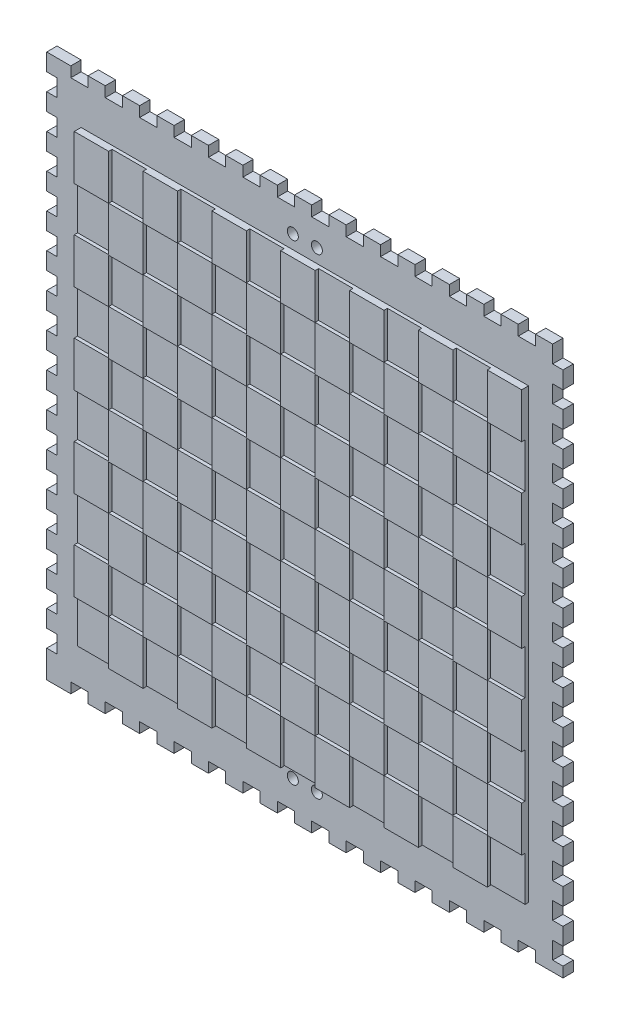
SolidWorks part; units mm, degrees
ref_plane "Front Plane" through (0, 0, 0) normal (0, 0, 1) x (1, 0, 0)
ref_plane "Top Plane" through (0, 0, 0) normal (0, 1, 0) x (1, 0, 0)
ref_plane "Right Plane" through (0, 0, 0) normal (1, 0, 0) x (0, 0, -1)
sketch "Sketch1" plane through (0, 0, 0) normal (0, 0, 1) x (1, 0, 0)
  line L5 (-75, 79) -> (75, 79)
  line L6 (-75, 79) -> (-75, -79)
  line L7 (-75, -79) -> (75, -79)
  line L8 (75, 79) -> (75, -79)
  line L9 (-75, 79) -> (75, -79) construction
  line L10 (-75, -79) -> (75, 79) construction
  point P0 (0, 0)
  dimension "D1" = 158
  dimension "D2" = 150
extrude "Boss-Extrude1" add sketch "Sketch1" along normal blind 5
sketch "Sketch2" plane through (0, 0, 5) normal (0, 0, 1) x (1, 0, 0)
  line L1 (-65, 65) -> (65, 65)
  line L2 (-65, 65) -> (-65, -65)
  line L3 (-65, -65) -> (65, -65)
  line L4 (65, 65) -> (65, -65)
  line L5 (-65, 65) -> (65, -65) construction
  line L6 (-65, -65) -> (65, 65) construction
  point P0 (0, 0)
  dimension "D1" = 130
  dimension "D2" = 130
extrude "Cut-Extrude1" cut sketch "Sketch2" against normal blind 1
sketch "Sketch3" plane through (0, 0, 4) normal (0, 0, 1) x (1, 0, 0)
  line L1 (-65, 65) -> (-55, 65)
  line L2 (-65, 65) -> (-65, 51.9)
  line L3 (-65, 51.9) -> (-55, 51.9)
  line L4 (-55, 65) -> (-55, 51.9)
  dimension "D1" = 13.1
  dimension "D2" = 10
extrude "Boss-Extrude2" add sketch "Sketch3" along normal blind 1
sketch "Sketch5" plane through (0, 0, 5) normal (0, 0, 1) x (1, 0, 0)
  line L1 (65, -65) -> (-65, -65)
  line L2 (65, -65) -> (65, 65)
  line L3 (65, 65) -> (-65, 65)
  line L4 (-65, -65) -> (-65, 65)
  line L9 (-75, -79) -> (75, -79)
  line L10 (-75, -79) -> (-75, 79)
  line L11 (-75, 79) -> (75, 79)
  line L12 (75, -79) -> (75, 79)
  dimension "D1" = 130
  dimension "D2" = 130
extrude "Cut-Extrude6" cut sketch "Sketch5" against normal blind 2
pattern_linear "LPattern3" count 7 spacing 20 along (1, 0, 0) count 5 spacing 26 along (0, -1, 0) of "Boss-Extrude2"
sketch "Sketch11" plane through (0, 0, 4) normal (0, 0, 1) x (1, 0, 0)
  line L0 (65, 65) -> (-65, 65) construction
  line L1 (-55, 51.95) -> (-45, 51.95)
  line L2 (-55, 51.95) -> (-55, 38.85)
  line L3 (-55, 38.85) -> (-45, 38.85)
  line L4 (-45, 51.95) -> (-45, 38.85)
  line L5 (-65, 65) -> (-65, -65) construction
  dimension "D1" = 13.1
  dimension "D2" = 10
  dimension "D3" = 13.05
  dimension "D4" = 10
extrude "Boss-Extrude4" add sketch "Sketch11" along normal blind 1
pattern_linear "LPattern4" count 6 spacing 20 along (1, 0, 0) count 5 spacing 26 along (0, -1, 0) of "Boss-Extrude4"
sketch "Sketch12" plane through (0, 0, 3) normal (0, 0, 1) x (1, 0, 0)
  line L1 (75, 79) -> (72, 79)
  line L2 (75, 79) -> (75, 74)
  line L3 (75, 74) -> (72, 74)
  line L4 (72, 79) -> (72, 74)
  dimension "D1" = 3
  dimension "D2" = 5
extrude "Cut-Extrude10" cut sketch "Sketch12" against normal through all
pattern_linear "LPattern5" count 16 spacing 10 along (0, -1, 0) of "Cut-Extrude10"
sketch "Sketch13" plane through (0, 0, 3) normal (0, 0, 1) x (1, 0, 0)
  line L0 (72, 79) -> (-75, 79) construction
  line L1 (67, 79) -> (62, 79)
  line L2 (67, 79) -> (67, 76)
  line L3 (67, 76) -> (62, 76)
  line L4 (62, 79) -> (62, 76)
  line L5 (72, 79) -> (72, 74) construction
  dimension "D1" = 5
  dimension "D2" = 3
  dimension "D3" = 5
extrude "Cut-Extrude11" cut sketch "Sketch13" against normal blind 3
pattern_linear "LPattern6" count 14 spacing 10 along (-1, 0, 0) of "Cut-Extrude11"
sketch "Sketch14" plane through (0, 0, 3) normal (0, 0, 1) x (1, 0, 0)
  line L0 (-75, -79) -> (75, -79) construction
  line L1 (67, -79) -> (62, -79)
  line L2 (67, -79) -> (67, -76)
  line L3 (67, -76) -> (62, -76)
  line L4 (62, -79) -> (62, -76)
  dimension "D1" = 5
  dimension "D2" = 3
  dimension "D3" = 5
extrude "Cut-Extrude12" cut sketch "Sketch14" against normal blind 3
pattern_linear "LPattern7" count 14 spacing 10 along (-1, 0, 0) of "Cut-Extrude12"
sketch "Sketch15" plane through (0, 0, 3) normal (0, 0, 1) x (1, 0, 0)
  line L0 (-75, 79) -> (-75, -79) construction
  line L1 (-75, 74) -> (-72, 74)
  line L2 (-75, 74) -> (-75, 69)
  line L3 (-75, 69) -> (-72, 69)
  line L4 (-72, 74) -> (-72, 69)
  line L5 (-68, 79) -> (-75, 79) construction
  dimension "D1" = 5
  dimension "D2" = 5
  dimension "D3" = 3
extrude "Cut-Extrude13" cut sketch "Sketch15" against normal blind 10
pattern_linear "LPattern8" count 15 spacing 10 along (0, -1, 0) of "Cut-Extrude13"
sketch "Sketch16" plane through (0, 0, 3) normal (0, 0, 1) x (1, 0, 0)
  line L0 (-8, 76) -> (-3, 76) construction
  line L1 (2, 76) -> (7, 76) construction
  circle A0 centre (-3.5, 69) radius 1.6
  circle A1 centre (3.5, 69) radius 1.6
  dimension "D1" = 3.2
  dimension "D2" = 3.2
  dimension "D3" = 3.5
  dimension "D4" = 3.5
  dimension "D5" = 7
  dimension "D6" = 7
extrude "Cut-Extrude14" cut sketch "Sketch16" against normal blind 15
sketch "Sketch17" plane through (0, 0, 3) normal (0, 0, 1) x (1, 0, 0)
  line L0 (-3, -76) -> (-8, -76) construction
  line L1 (7, -76) -> (2, -76) construction
  circle A0 centre (3.5, -68) radius 1.6
  circle A1 centre (-3.5, -68) radius 1.6
  dimension "D1" = 3.2
  dimension "D2" = 3.2
  dimension "D3" = 3.5
  dimension "D4" = 3.5
  dimension "D5" = 8
  dimension "D6" = 8
extrude "Cut-Extrude15" cut sketch "Sketch17" against normal blind 10
